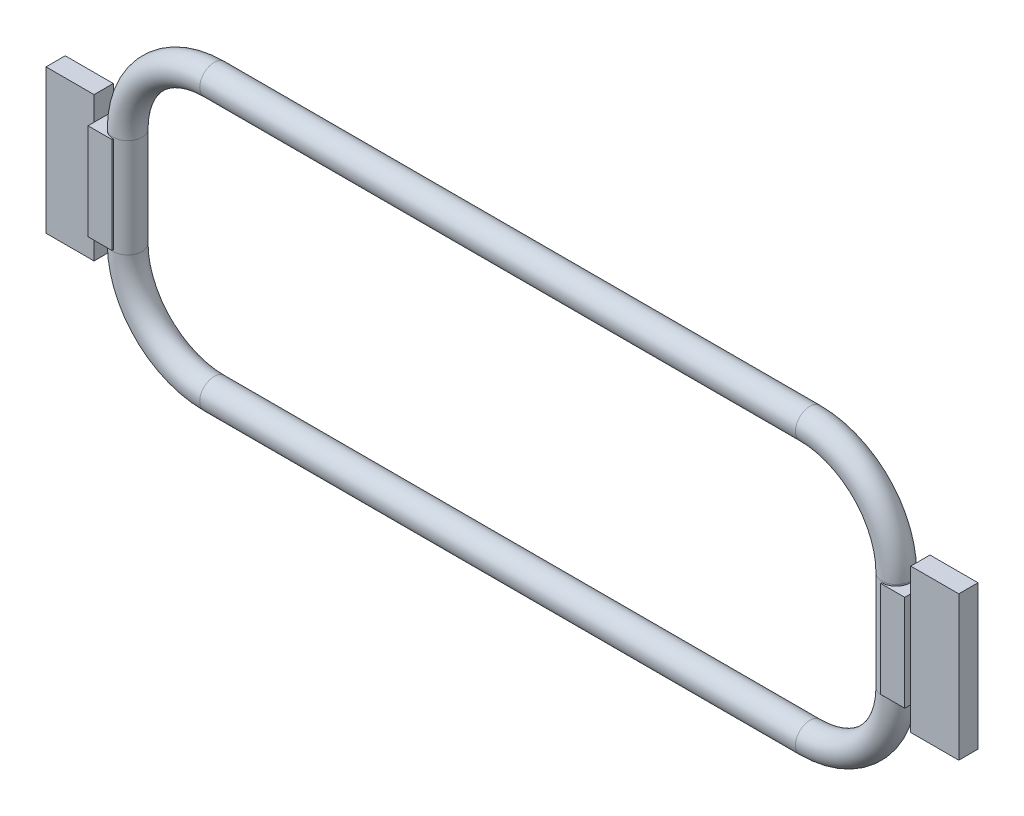
SolidWorks part; units mm, degrees
ref_plane "Front Plane" through (0, 0, 0) normal (0, 0, 1) x (1, 0, 0)
ref_plane "Top Plane" through (0, 0, 0) normal (0, 1, 0) x (1, 0, 0)
ref_plane "Right Plane" through (0, 0, 0) normal (1, 0, 0) x (0, 0, -1)
sketch "Sketch1" plane through (0, 0, 0) normal (0, 0, 1) x (1, 0, 0)
  line L0 (50, 0) -> (-900, 0)
  line L1 (-50, 75) -> (50, 75)
  line L2 (-50, 75) -> (-50, -75)
  line L3 (-50, -75) -> (50, -75)
  line L4 (50, 75) -> (50, -75)
  line L5 (-50, 75) -> (50, -75) construction
  line L6 (-50, -75) -> (50, 75) construction
  line L8 (-800, 75) -> (-900, 75)
  line L9 (-800, 75) -> (-800, -75)
  line L10 (-800, -75) -> (-900, -75)
  line L11 (-900, 75) -> (-900, -75)
  line L12 (-800, 75) -> (-900, -75) construction
  line L13 (-800, -75) -> (-900, 75) construction
  point P0 (0, 0)
  point P8 (-850, 0)
  point P13 (-837.3807, 0)
  point P14 (-881.5532, 0)
  point P15 (-856.2505, 0)
extrude "Boss-Extrude1" add sketch "Sketch1" along normal blind 20 contours L8 L11 L0 L9 | L0 L11 L10 L9 | L4 L3 L2 L1 region at (-850, -37.5, 0) region at (-850, 37.5, 0)
sketch "Sketch4" plane through (0, 0, 0) normal (0, 0, -1) x (-1, 0, 0)
  line L0 (50, -75) -> (-50, -75) construction
  line L1 (50, 75) -> (0, 75)
  line L2 (50, 75) -> (50, -75)
  line L3 (50, -75) -> (0, -75)
  line L4 (0, 75) -> (0, -75)
  line L5 (800, -75) -> (900, -75) construction
  line L6 (800, 75) -> (850, 75)
  line L7 (800, 75) -> (800, -75)
  line L8 (800, -75) -> (850, -75)
  line L9 (850, 75) -> (850, -75)
extrude "Boss-Extrude3" add sketch "Sketch4" along normal blind 6.25
sketch "Sketch5" plane through (0, 0, 20) normal (0, 0, 1) x (1, 0, 0)
  line L0 (-800, -75) -> (-900, -75) construction
  line L1 (-800, 75) -> (-850, 75)
  line L2 (-800, 75) -> (-800, -75)
  line L3 (-800, -75) -> (-850, -75)
  line L4 (-850, 75) -> (-850, -75)
  line L5 (-50, -75) -> (50, -75) construction
  line L6 (-50, 75) -> (0, 75)
  line L7 (-50, 75) -> (-50, -75)
  line L8 (-50, -75) -> (0, -75)
  line L9 (0, 75) -> (0, -75)
extrude "Boss-Extrude4" add sketch "Sketch5" along normal blind 6.25
sketch "Sketch21" plane through (0, 75, 0) normal (0, 1, 0) x (1, 0, 0)
  line L1 (-850, 6.25) -> (0, 6.25)
  line L2 (-850, 6.25) -> (-850, -26.25)
  line L3 (-850, -26.25) -> (0, -26.25)
  line L4 (0, 6.25) -> (0, -26.25)
extrude "Cut-Extrude2" cut sketch "Sketch21" against normal blind 25
extrude "Cut-Extrude3" cut sketch "Sketch21<2>" along normal blind 25 from surface starting at face at (-850, -75, 10)
sketch "Sketch21<2>" plane through (0, 75, 0) normal (0, 1, 0) x (1, 0, 0) same geometry as "Sketch21"
ref_plane "Plane4" through (0, 0, 10) normal (0, 0, 1) x (1, 0, 0)
sketch "Sketch6" plane through (0, 0, 10) normal (0, 0, 1) x (1, 0, 0)
  line L7 (-425, 124.002) -> (-425, -127.0479) construction
  line L9 (-800, 0) -> (-425, 0) construction
  line L10 (-115, -141.5049) -> (-735, -141.5049)
  line L11 (-25, -51.5049) -> (-25, 51.5049)
  line L12 (-115, 141.5049) -> (-735, 141.5049)
  line L13 (-825, -51.5049) -> (-825, 51.5049)
  line L14 (-25, -141.5049) -> (-825, 141.5049) construction
  line L15 (-25, 141.5049) -> (-825, -141.5049) construction
  line L16 (-800, -50) -> (-800, 50) construction
  arc A0 (-735, -141.5049) -> (-825, -51.5049) centre (-735, -51.5049) cw
  arc A1 (-115, -141.5049) -> (-25, -51.5049) centre (-115, -51.5049) ccw
  arc A2 (-25, 51.5049) -> (-115, 141.5049) centre (-115, 51.5049) ccw
  arc A3 (-735, 141.5049) -> (-825, 51.5049) centre (-735, 51.5049) ccw
  point P0 (-425, 0)
  point P11 (0, 0)
  dimension "D1" = 90
sweep "Sweep1" add path "Sketch6" circular profile diameter 30 parameters "D3"=30
ref_plane "Plane5" through (0, 0, 0) normal (0, 1, 0) x (1, 0, 0)
sketch "Sketch19" plane through (0, 0, 0) normal (0, 1, 0) x (1, 0, 0)
  line L0 (-825, -26.25) -> (-825, -25)
  line L3 (-425, -10) -> (-425, -84.3273) construction
  line L4 (-850, -26.25) -> (-800, -26.25) construction
  line L5 (-825, 6.25) -> (-800, 6.25)
  line L6 (-825, 5) -> (-825, 6.25)
  line L7 (-800, 6.25) -> (-850, 6.25) construction
  line L8 (-800, 6.25) -> (-800, -26.25)
  line L9 (-800, -26.25) -> (-825, -26.25)
  line L10 (-50, -26.25) -> (-25, -26.25)
  line L11 (-50, 6.25) -> (-50, -26.25)
  line L12 (-25, 5) -> (-25, 6.25)
  line L13 (-25, 6.25) -> (-50, 6.25)
  line L14 (-25, -26.25) -> (-25, -25)
  arc A0 (-825, -25) -> (-825, 5) centre (-825, -10) ccw
  arc A1 (-25, -25) -> (-25, 5) centre (-25, -10) cw
extrude "Cut-Extrude1" cut sketch "Sketch19" against normal mid plane 100
